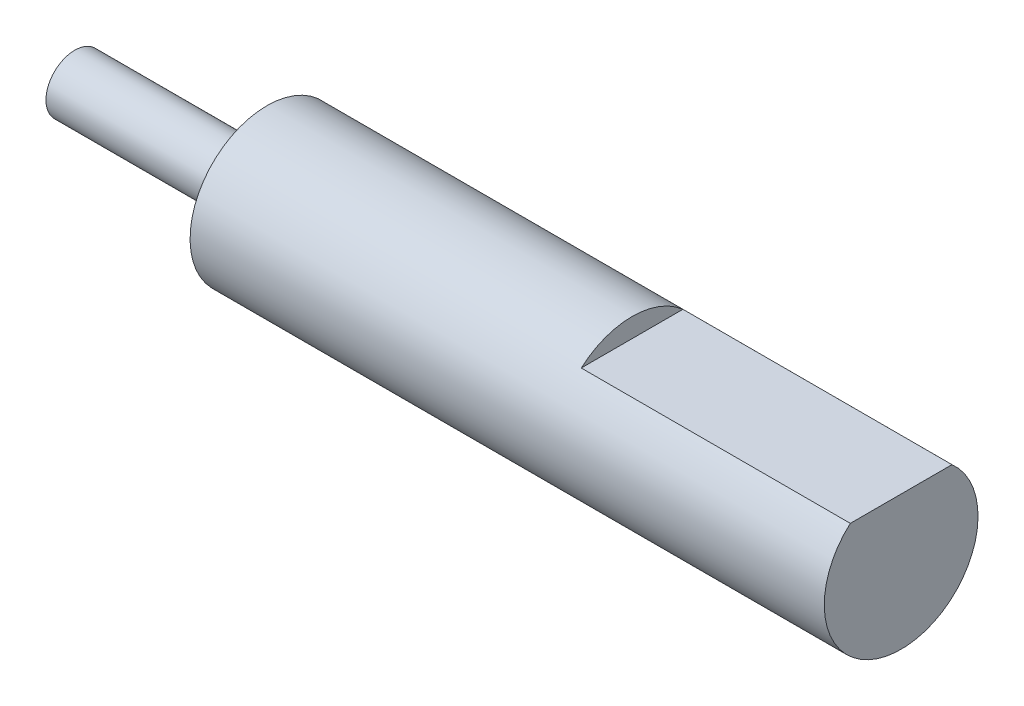
SolidWorks part; units mm, degrees
material "ASTM A36 Steel"
ref_plane "Front Plane" through (0, 0, 0) normal (0, 0, 1) x (1, 0, 0)
ref_plane "Top Plane" through (0, 0, 0) normal (0, 1, 0) x (1, 0, 0)
ref_plane "Right Plane" through (0, 0, 0) normal (1, 0, 0) x (0, 0, -1)
sketch "Sketch1" plane through (0, 0, 0) normal (1, 0, 0) x (0, 0, -1)
  line L0 (2.6458, 3) -> (-2.6458, 3)
  circle A0 centre (0, 0) radius 4
  circle A1 centre (0, 0) radius 1.5
  dimension "D1" = 8
  dimension "D2" = 3
  dimension "D3" = 3
extrude "Boss-Extrude1" add sketch "Sketch1" against normal blind 10 contours A1 region at (0, 0, 0)
extrude "Boss-Extrude2" add sketch "Sketch1<3>" along normal blind 33 contours L0 A0 A1 | A1 region at (0, 1.602, -3.5489) region at (0, 0, 0)
sketch "Sketch1<3>" plane through (0, 0, 0) normal (1, 0, 0) x (0, 0, -1) same geometry as "Sketch1"
extrude "Boss-Extrude3" add sketch "Sketch1<4>" along normal blind 19 contours L0 A0 region at (0, 3.4046, 0)
sketch "Sketch1<4>" plane through (0, 0, 0) normal (1, 0, 0) x (0, 0, -1) same geometry as "Sketch1"
